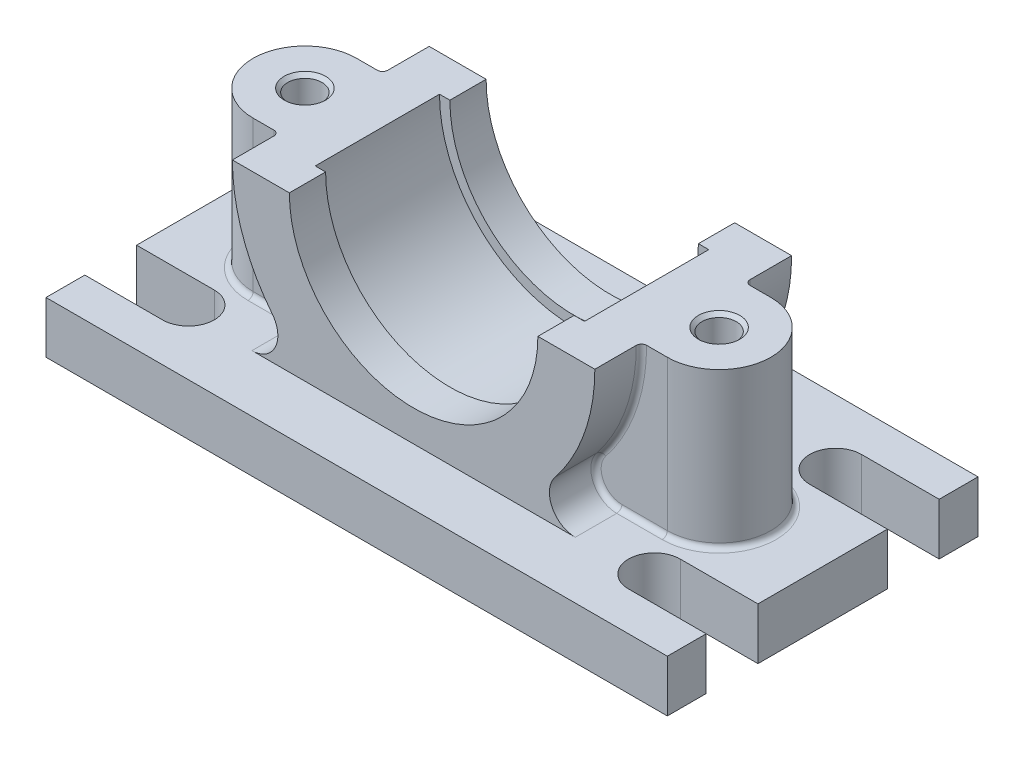
SolidWorks part; units mm, degrees
material "Сталь"
ref_plane "Спереди" through (0, 0, 0) normal (0, 0, 1) x (1, 0, 0)
ref_plane "Сверху" through (0, 0, 0) normal (0, 1, 0) x (1, 0, 0)
ref_plane "Справа" through (0, 0, 0) normal (1, 0, 0) x (0, 0, -1)
sketch "Эскиз1" plane through (0, 0, 0) normal (0, 0, 1) x (1, 0, 0)
  line L0 (-35, 0) -> (35, 0)
  circle A0 centre (0, 0) radius 24
  circle A1 centre (0, 0) radius 35
  circle A2 centre (0, 0) radius 26
  dimension "D1" = 48
  dimension "D2" = 70
  dimension "D3" = 52
extrude "Бобышка-Вытянуть2" add sketch "Эскиз1" along normal mid plane 38 contours A2 L0 A1 | L0 A2 A0 region at (25, -0.5814, 0) region at (30.5, -0.7826, 0)
sketch "Эскиз2" plane through (0, 0, 0) normal (0, 1, 0) x (1, 0, 0)
  line L0 (-40, 0) -> (40, 0) construction
  line L1 (-40, 10) -> (40, 10)
  line L2 (-40, -10) -> (40, -10)
  arc A0 (-40, 10) -> (-40, -10) centre (-40, 0) ccw
  arc A1 (40, -10) -> (40, 10) centre (40, 0) ccw
  point P2 (0, 0)
  dimension "D1" = 40
  dimension "D2" = 10
extrude "Бобышка-Вытянуть5" add sketch "Эскиз2" against normal blind 40
extrude "Вырез-Вытянуть1" cut sketch "Эскиз1<4>" against normal up to surface and the other way up to surface contours A0 up to face at (0, -14.75, -19) other way up to face at (0, -14.75, 19)
sketch "Эскиз1<4>" plane through (0, 0, 0) normal (0, 0, 1) x (1, 0, 0) same geometry as "Эскиз1"
sketch "Эскиз4" plane through (0, -40, 0) normal (0, -1, 0) x (1, 0, 0)
  line L1 (-60, -30) -> (60, -30)
  line L2 (-60, -30) -> (-60, 30)
  line L3 (-60, 30) -> (60, 30)
  line L4 (60, -30) -> (60, 30)
  line L5 (-60, -30) -> (60, 30) construction
  line L6 (-60, 30) -> (60, -30) construction
  point P0 (0, 0)
  dimension "D1" = 120
  dimension "D2" = 60
extrude "Бобышка-Вытянуть6" add sketch "Эскиз4" against normal blind 10
fillet "Скругление2" radius 5 4 edges at (18.0278, -30, 14.5) (18.0278, -30, -14.5) (-18.0278, -30, -14.5) (-18.0278, -30, 14.5)
sketch "Эскиз5" plane through (0, -40, 0) normal (0, -1, 0) x (1, 0, 0)
  line L0 (-60, 0) -> (60, 0) construction
  line L1 (-60, 30) -> (-60, -30) construction
  line L2 (60, -30) -> (60, 30) construction
  line L3 (75, -17.5) -> (45, -17.5) construction
  line L4 (75, -22.5) -> (45, -22.5)
  line L5 (75, -12.5) -> (45, -12.5)
  arc A0 (75, -22.5) -> (75, -12.5) centre (75, -17.5) ccw
  arc A1 (45, -12.5) -> (45, -22.5) centre (45, -17.5) ccw
  point P8 (60, -17.5)
  dimension "D1" = 10
  dimension "D2" = 15
  dimension "D3" = 35
extrude "Вырез-Вытянуть2" cut sketch "Эскиз5" against normal through all
mirror "Зеркальное отражение1" about plane through (0, 0, 0) normal (0, 0, 1) of "Вырез-Вытянуть2"
mirror "Зеркальное отражение2" about plane through (0, 0, 0) normal (1, 0, 0) of "Зеркальное отражение1"
extrude "Вырез-Вытянуть3" cut sketch "Эскиз1<5>" against normal mid plane 24 contours L0 A2 A0 region at (25, -0.5814, 0)
sketch "Эскиз1<5>" plane through (0, 0, 0) normal (0, 0, 1) x (1, 0, 0) same geometry as "Эскиз1"
sketch "Эскиз6" plane through (0, 0, 0) normal (0, 0, 1) x (1, 0, 0)
  line L0 (0, -34) -> (0, -40)
  line L1 (60, -40) -> (-60, -40) construction
  line L2 (0, -40) -> (25, -40)
  line L3 (25, -40) -> (25, -23.0434)
  arc A2 (-34, 0) -> (34, 0) centre (0, 0) ccw
  arc A3 (0, -34) -> (25, -23.0434) centre (0, 0) ccw
  dimension "D2" = 25
  dimension "D1" = 10
extrude "Вырез-Вытянуть4" cut sketch "Эскиз6" against normal mid plane 24 contours L3 A3 L0 L2
mirror "Зеркальное отражение3" about plane through (0, -34, -12) normal (-1, 0, 0) of "Вырез-Вытянуть4"
fillet "Скругление3" radius 4 2 edges at (25, -23.0434, 0) (-25, -23.0434, 0)
fillet "Скругление4" radius 2 14 edges at (-25, -35.8351, 12) (-22.8918, -28.1458, 12) (25, -35.8351, 12) (22.8918, -28.1458, 12) (-25, -35.8351, -12) (-22.8918, -28.1458, -12) (25, -35.8351, -12) (22.8918, -28.1458, -12) (0, -34, 12) (0, -34, -12) (0, -40, 12) (-25, -40, 0) (25, -40, 0) (0, -40, -12)
sketch "Эскиз7" plane through (0, 0, 0) normal (0, 1, 0) x (1, 0, 0)
  circle A0 centre (-40, 0) radius 3.3095
  circle A1 centre (40, 0) radius 3.3095
  dimension "D1" = 6.619
extrude "Вырез-Вытянуть5" cut sketch "Эскиз7" against normal blind 25
cosmetic thread "Условное изображение резьбы1" parameters "D2"=8
cosmetic thread "Условное изображение резьбы2" parameters "D2"=8
fillet "Скругление5" radius 1 14 edges at (33.0247, -11.5917, -10) (26.7181, -27.1651, -10) (35.6125, -30, -10) (50, -30, 0) (35.6125, -30, 10) (26.7181, -27.1651, 10) (-33.0247, -11.5917, 10) (-26.7181, -27.1651, 10) (-33.0247, -11.5917, -10) (-26.7181, -27.1651, -10) (-35.6125, -30, -10) (-50, -30, 0) (33.0247, -11.5917, 10) (-35.6125, -30, 10)
chamfer "Фаска1" distance 3.3 angle 45 2 edges at (40, -25, 3.3095) (-40, -25, 3.3095)
chamfer "Фаска2" distance 0.6905 angle 45 2 edges at (40, 0, 3.3095) (-40, 0, 3.3095)
